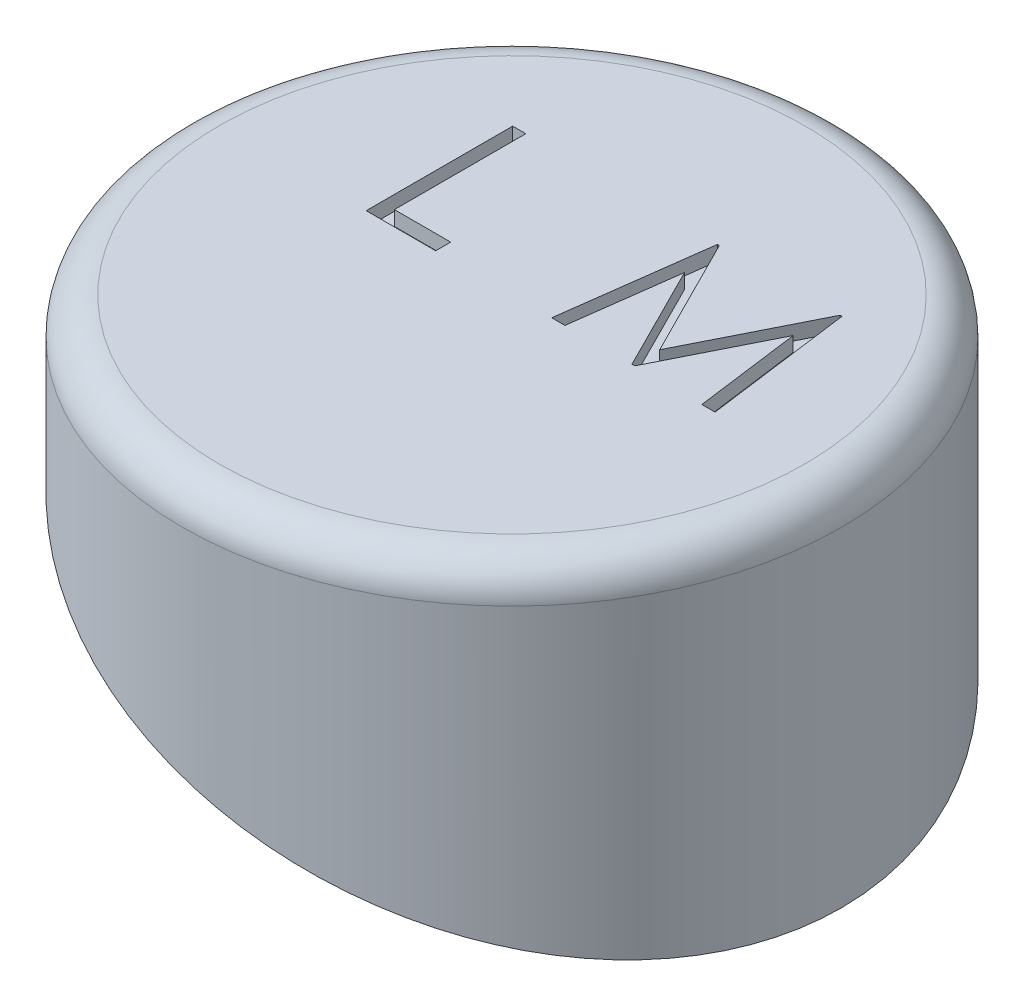
SolidWorks part; units mm, degrees
ref_plane "Front Plane" through (0, 0, 0) normal (0, 0, 1) x (1, 0, 0)
ref_plane "Top Plane" through (0, 0, 0) normal (0, 1, 0) x (1, 0, 0)
ref_plane "Right Plane" through (0, 0, 0) normal (1, 0, 0) x (0, 0, -1)
sketch "Sketch1" plane through (0, 0, 0) normal (0, 1, 0) x (1, 0, 0)
  circle A0 centre (0, 0) radius 45
  dimension "D1" = 90
extrude "Boss-Extrude1" add sketch "Sketch1" along normal blind 50
sketch "Sketch2" plane through (0, 0, 0) normal (0, 0, 1) x (1, 0, 0)
  line L0 (45, 0) -> (-45, 0)
  line L1 (-45, 0) -> (-45, 30.9895)
  line L2 (-45, 50) -> (-45, 0) construction
  line L3 (-45, 30.9895) -> (45, 0)
  dimension "D1" = 19
extrude "Cut-Extrude1" cut sketch "Sketch2" against normal up to body and the other way up to body separate body
fillet "Fillet1" radius 5 1 edges at (0, 50, 45)
sketch "Sketch4" plane through (0, 50, 0) normal (0, 1, 0) x (1, 0, 0)
  line L0 (-22.4738, 0) -> (22.4738, 0) construction
  text T0 "LM\r\n" font "Century Gothic" height 20
  point P4 (0, 0)
extrude "Cut-Extrude2" cut sketch "Sketch4" against normal blind 2
shell "Shell1" thickness 5 removed face at (45, 0, 0)
